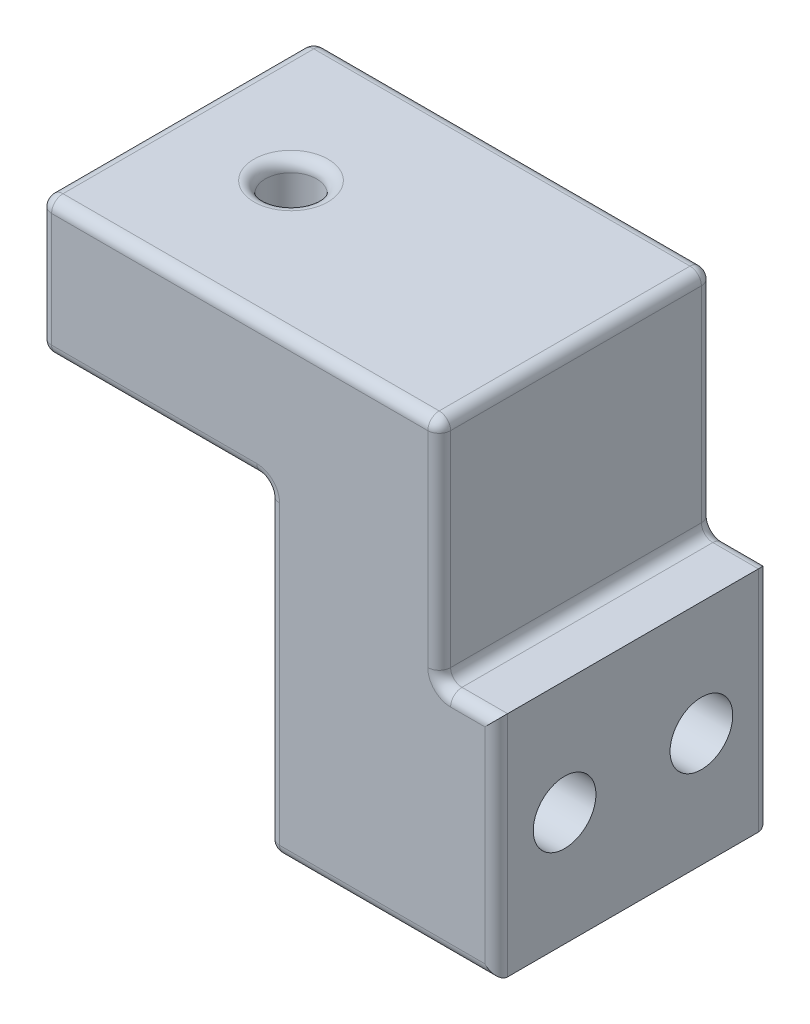
SolidWorks part; units mm, degrees
material "PLA"
ref_plane "Alzado" through (0, 0, 0) normal (0, 0, 1) x (1, 0, 0)
ref_plane "Planta" through (0, 0, 0) normal (0, 1, 0) x (1, 0, 0)
ref_plane "Vista lateral" through (0, 0, 0) normal (1, 0, 0) x (0, 0, -1)
sketch "Sketch4" plane through (0, 0, 0) normal (0, 1, 0) x (1, 0, 0)
  line L1 (0, 0) -> (40, 0)
  line L2 (0, 0) -> (0, 24)
  line L3 (0, 24) -> (40, 24)
  line L4 (40, 0) -> (40, 24)
  dimension "D1" = 24
  dimension "D2" = 40
extrude "Boss-Extrude2" add sketch "Sketch4" along normal blind 40
sketch "Sketch6" plane through (0, 0, 0) normal (0, 0, 1) x (1, 0, 0)
  line L0 (0, 40) -> (35, 40)
  line L1 (0, 40) -> (40, 40) construction
  line L2 (35, 40) -> (35, 20)
  line L3 (35, 20) -> (40, 20)
  line L4 (40, 40) -> (40, 0) construction
  line L5 (40, 20) -> (40, 0)
  line L6 (40, 0) -> (20, 0)
  line L7 (0, 0) -> (40, 0) construction
  line L8 (20, 0) -> (20, 28)
  line L9 (20, 28) -> (0, 28)
  line L10 (0, 40) -> (0, 0) construction
  line L11 (0, 28) -> (0, 40)
  line L12 (35, 40) -> (40, 40)
  line L13 (40, 40) -> (40, 20)
  line L14 (0, 28) -> (0, 0)
  line L15 (0, 0) -> (20, 0)
  line M9 (0, 0) -> (40, 0)
  line M10 (40, 0) -> (40, 40)
  line M11 (40, 40) -> (0, 40)
  line M12 (0, 40) -> (0, 0)
  dimension "D1" = 5
  dimension "D2" = 20
  dimension "D3" = 20
  dimension "D4" = 12
extrude "Cut-Extrude1" cut sketch "Sketch6" against normal through all contours L2 L3 M10 M11 | L8 L9 M12 M9 region at (37.5, 30, 0) region at (10, 14, 0)
sketch "Sketch7" plane through (0, 28, 0) normal (0, -1, 0) x (-1, 0, 0)
  line L0 (-10, 0) -> (-10, 24) construction
  line L1 (-20, 0) -> (0, 0) construction
  line L2 (-20, 24) -> (0, 24) construction
  circle A0 centre (-10, 12) radius 2.25
  dimension "D1" = 4.5
extrude "Cut-Extrude2" cut sketch "Sketch7" against normal through all
sketch "Sketch8" plane through (20, 0, 0) normal (-1, 0, 0) x (0, 0, 1)
  line L0 (0, 10) -> (-24, 10) construction
  line L1 (0, 0) -> (0, 28) construction
  line L2 (-24, 0) -> (-24, 28) construction
  line L3 (-24, 0) -> (0, 0) construction
  circle A0 centre (-10, 10) radius 2.5
  circle A1 centre (-14, 10) radius 2.5
  dimension "D2" = 10
  dimension "D4" = 5
  dimension "D5" = 5
  dimension "D1" = 10
  dimension "D3" = 10
sketch "Sketch10" plane through (20, 0, 0) normal (-1, 0, 0) x (0, 0, 1)
  line L0 (-24, 10) -> (0, 10) construction
  line L1 (-24, 0) -> (-24, 28) construction
  line L2 (0, 0) -> (0, 28) construction
  line L3 (-24, 0) -> (0, 0) construction
  circle A0 centre (-18, 10) radius 2.75
  circle A1 centre (-6, 10) radius 2.75
  dimension "D1" = 5.5
  dimension "D2" = 5.5
  dimension "10" = 10
  dimension "D3" = 6
  dimension "D4" = 6
extrude "Cut-Extrude4" cut sketch "Sketch10" against normal through all
sketch "Sketch12" plane through (20, 0, 0) normal (-1, 0, 0) x (0, 0, 1)
  line L0 (-24, 10) -> (0, 10) construction
  line L1 (-24, 0) -> (-24, 28) construction
  line L2 (0, 0) -> (0, 28) construction
  line L3 (-24, 0) -> (0, 0) construction
  circle A0 centre (-18, 10) radius 4.5
  circle A1 centre (-6, 10) radius 4.5
  dimension "D1" = 9
  dimension "D2" = 9
  dimension "10" = 10
extrude "Cut-Extrude5" cut sketch "Sketch12" against normal blind 8
sketch "Sketch13" plane through (0, 40, 0) normal (0, 1, 0) x (1, 0, 0)
  line L0 (0, 0) -> (35, 0) construction
  line L1 (7.9793, 8.5) -> (12.0207, 8.5)
  line L2 (12.0207, 8.5) -> (14.0415, 12)
  line L3 (14.0415, 12) -> (12.0207, 15.5)
  line L4 (12.0207, 15.5) -> (7.9793, 15.5)
  line L5 (7.9793, 15.5) -> (5.9585, 12)
  line L6 (5.9585, 12) -> (7.9793, 8.5)
  circle A0 centre (10, 12) radius 3.5 construction
  dimension "D1" = 7
extrude "Cut-Extrude6" [suppressed] cut sketch "Sketch13" against normal blind 3
fillet "Fillet1" radius 1 25 edges at (35, 20, -12) (10, 28, -24) (30, 0, -24) (40, 10, -24) (37.5, 20, -24) (35, 30, -24) (40, 10, 0) (30, 0, 0) (10, 28, 0) (35, 30, 0) (37.5, 20, 0) (17.5, 40, -24) (35, 40, -12) (17.5, 40, 0) (10, 40, -14.25) (0, 40, -12) (0, 34, 0) (0, 28, -12) (0, 34, -24) (20, 0, -12) (20, 14, -24) (20, 28, -12) (20, 14, 0) (20, 10, -1.5) (20, 10, -13.5)
fillet "Fillet2" [suppressed] radius 1
sketch "Sketch14" plane through (0, 28, 0) normal (0, -1, 0) x (1, 0, 0)
  line L0 (1, -1) -> (1, -23) construction
  line L1 (6.5, -14.0207) -> (10, -16.0415)
  line L2 (10, -16.0415) -> (13.5, -14.0207)
  line L3 (13.5, -14.0207) -> (13.5, -9.9793)
  line L4 (13.5, -9.9793) -> (10, -7.9585)
  line L5 (10, -7.9585) -> (6.5, -9.9793)
  line L6 (6.5, -9.9793) -> (6.5, -14.0207)
  circle A0 centre (10, -12) radius 3.5 construction
  dimension "D1" = 7
extrude "Cut-Extrude7" cut sketch "Sketch14" against normal blind 5
